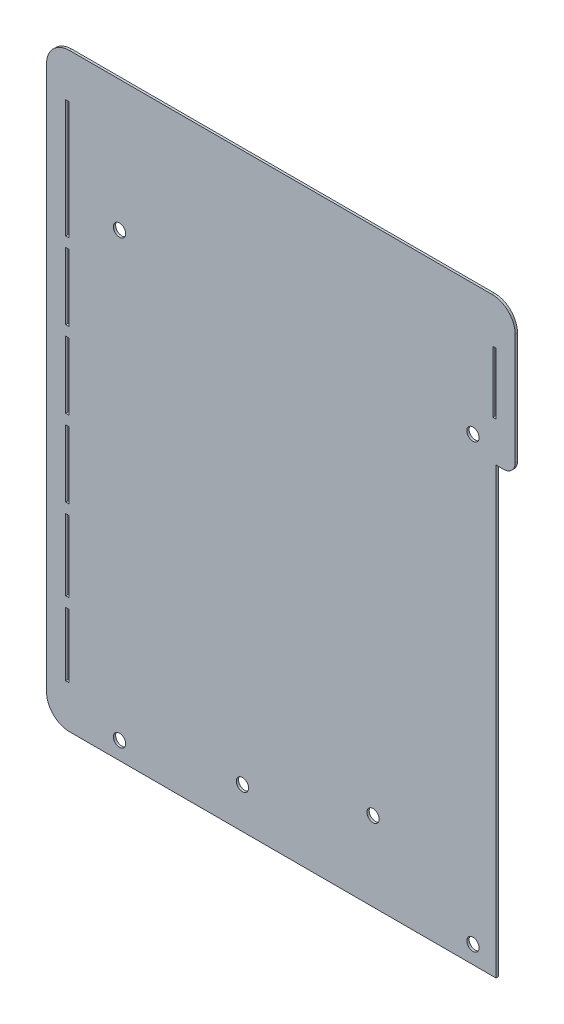
SolidWorks part; units mm, degrees
material "Plain Carbon Steel"
ref_plane "Front Plane" through (0, 0, 0) normal (0, 0, 1) x (1, 0, 0)
ref_plane "Top Plane" through (0, 0, 0) normal (0, 1, 0) x (1, 0, 0)
ref_plane "Right Plane" through (0, 0, 0) normal (1, 0, 0) x (0, 0, -1)
sketch "Model" plane through (0, 0, 0) normal (0, 0, 1) x (1, 0, 0)
  line L0 (104.1673, 32.1811) -> (4.1672, 32.1811)
  line L1 (104.1673, 155.1806) -> (104.1673, 32.1811)
  line L2 (4.1672, 155.1806) -> (104.1673, 155.1806)
  line L3 (4.1672, 32.1811) -> (4.1672, 155.1806)
  line L4 (44.9158, 146.4259) -> (47.4224, 146.4259)
  line L5 (47.4224, 146.4259) -> (47.4224, 148.9326)
  line L6 (47.4224, 148.9326) -> (44.9158, 148.9326)
  line L7 (44.9158, 148.9326) -> (44.9158, 146.4259)
  line L8 (77.4127, 147.4278) -> (79.9193, 147.4278)
  line L9 (79.9193, 147.4278) -> (79.9193, 149.9344)
  line L10 (79.9193, 149.9344) -> (77.4127, 149.9344)
  line L11 (77.4127, 149.9344) -> (77.4127, 147.4278)
  line L12 (6.3266, 141.9721) -> (8.3592, 141.9721)
  line L13 (8.3592, 141.9721) -> (8.3592, 144.0047)
  line L14 (8.3592, 144.0047) -> (6.3266, 144.0047)
  line L15 (6.3266, 144.0047) -> (6.3266, 141.9721)
  line L16 (6.3266, 121.6529) -> (8.3592, 121.6529)
  line L17 (8.3592, 121.6529) -> (8.3592, 123.6855)
  line L18 (8.3592, 123.6855) -> (6.3266, 123.6855)
  line L19 (6.3266, 123.6855) -> (6.3266, 121.6529)
  line L20 (6.3266, 101.3324) -> (8.3592, 101.3324)
  line L21 (8.3592, 101.3324) -> (8.3592, 103.365)
  line L22 (8.3592, 103.365) -> (6.3266, 103.365)
  line L23 (6.3266, 103.365) -> (6.3266, 101.3324)
  line L24 (6.3266, 81.0118) -> (8.3592, 81.0118)
  line L25 (8.3592, 81.0118) -> (8.3592, 83.0444)
  line L26 (8.3592, 83.0444) -> (6.3266, 83.0444)
  line L27 (6.3266, 83.0444) -> (6.3266, 81.0118)
  line L28 (6.3266, 60.6927) -> (8.3592, 60.6927)
  line L29 (8.3592, 60.6927) -> (8.3592, 62.7253)
  line L30 (8.3592, 62.7253) -> (6.3266, 62.7253)
  line L31 (6.3266, 62.7253) -> (6.3266, 60.6927)
  line L32 (85.9221, 148.4144) -> (87.9547, 148.4144)
  line L33 (87.9547, 148.4144) -> (87.9547, 150.447)
  line L34 (87.9547, 150.447) -> (85.9221, 150.447)
  line L35 (85.9221, 150.447) -> (85.9221, 148.4144)
  line L36 (6.3266, 50.5324) -> (8.3592, 50.5324)
  line L37 (8.3592, 50.5324) -> (8.3592, 52.565)
  line L38 (8.3592, 52.565) -> (6.3266, 52.565)
  line L39 (6.3266, 52.565) -> (6.3266, 50.5324)
  line L40 (6.3266, 42.9118) -> (8.3592, 42.9118)
  line L41 (8.3592, 42.9118) -> (8.3592, 44.9444)
  line L42 (8.3592, 44.9444) -> (6.3266, 44.9444)
  line L43 (6.3266, 44.9444) -> (6.3266, 42.9118)
  line L44 (52.8726, 50.0418) -> (54.3815, 50.0418)
  line L45 (54.3815, 50.0418) -> (54.3815, 51.5508)
  line L46 (54.3815, 51.5508) -> (52.8726, 51.5508)
  line L47 (52.8726, 51.5508) -> (52.8726, 50.0418)
  line L48 (58.4219, 130.1637) -> (60.4545, 130.1637)
  line L49 (60.4545, 130.1637) -> (60.4545, 132.1963)
  line L50 (60.4545, 132.1963) -> (58.4219, 132.1963)
  line L51 (58.4219, 132.1963) -> (58.4219, 130.1637)
  line L52 (97.8807, 141.1439) -> (99.9133, 141.1439)
  line L53 (99.9133, 141.1439) -> (99.9133, 143.1765)
  line L54 (99.9133, 143.1765) -> (97.8807, 143.1765)
  line L55 (97.8807, 143.1765) -> (97.8807, 141.1439)
  line L56 (48.438, 37.3046) -> (48.438, 37.0552)
  line L57 (49.9456, 37.0552) -> (49.9456, 37.3046)
  line L58 (52.8877, 37.3046) -> (52.8877, 37.0552)
  line L59 (54.3967, 37.0552) -> (54.3967, 37.3046)
  line L60 (54.3126, 34.0993) -> (54.3126, 33.8995)
  line L61 (56.7201, 33.8995) -> (56.7201, 34.0993)
  line L62 (46.1133, 34.0993) -> (46.1133, 33.8995)
  line L63 (48.5207, 33.8995) -> (48.5207, 34.0993)
  line L64 (82.9607, 49.0165) -> (84.9933, 49.0165)
  line L65 (84.9933, 49.0165) -> (84.9933, 51.0492)
  line L66 (84.9933, 51.0492) -> (82.9607, 51.0492)
  line L67 (82.9607, 51.0492) -> (82.9607, 49.0165)
  line L68 (29.8828, 70.9163) -> (31.9154, 70.9163)
  line L69 (31.9154, 70.9163) -> (31.9154, 72.9489)
  line L70 (31.9154, 72.9489) -> (29.8828, 72.9489)
  line L71 (29.8828, 72.9489) -> (29.8828, 70.9163)
  line L72 (29.8828, 68.1658) -> (31.9154, 68.1658)
  line L73 (31.9154, 68.1658) -> (31.9154, 70.1984)
  line L74 (31.9154, 70.1984) -> (29.8828, 70.1984)
  line L75 (29.8828, 70.1984) -> (29.8828, 68.1658)
  line L76 (29.8828, 108.6649) -> (31.9154, 108.6649)
  line L77 (31.9154, 108.6649) -> (31.9154, 110.6975)
  line L78 (31.9154, 110.6975) -> (29.8828, 110.6975)
  line L79 (29.8828, 110.6975) -> (29.8828, 108.6649)
  line L80 (29.8828, 111.4141) -> (31.9154, 111.4141)
  line L81 (31.9154, 111.4141) -> (31.9154, 113.4467)
  line L82 (31.9154, 113.4467) -> (29.8828, 113.4467)
  line L83 (29.8828, 113.4467) -> (29.8828, 111.4141)
  line L84 (29.8828, 91.1652) -> (31.9154, 91.1652)
  line L85 (31.9154, 91.1652) -> (31.9154, 93.1978)
  line L86 (31.9154, 93.1978) -> (29.8828, 93.1978)
  line L87 (29.8828, 93.1978) -> (29.8828, 91.1652)
  line L88 (29.8828, 88.4147) -> (31.9154, 88.4147)
  line L89 (31.9154, 88.4147) -> (31.9154, 90.4473)
  line L90 (31.9154, 90.4473) -> (29.8828, 90.4473)
  line L91 (29.8828, 90.4473) -> (29.8828, 88.4147)
  line L92 (29.8828, 128.6658) -> (31.9154, 128.6658)
  line L93 (31.9154, 128.6658) -> (31.9154, 130.6984)
  line L94 (31.9154, 130.6984) -> (29.8828, 130.6984)
  line L95 (29.8828, 130.6984) -> (29.8828, 128.6658)
  line L96 (29.8828, 131.4163) -> (31.9154, 131.4163)
  line L97 (31.9154, 131.4163) -> (31.9154, 133.4489)
  line L98 (31.9154, 133.4489) -> (29.8828, 133.4489)
  line L99 (29.8828, 133.4489) -> (29.8828, 131.4163)
  line L100 (48.1611, 135.1453) -> (50.1937, 135.1453)
  line L101 (50.1937, 135.1453) -> (50.1937, 137.1779)
  line L102 (50.1937, 137.1779) -> (48.1611, 137.1779)
  line L103 (48.1611, 137.1779) -> (48.1611, 135.1453)
  line L104 (11.4074, 121.6529) -> (13.44, 121.6529)
  line L105 (13.44, 121.6529) -> (13.44, 123.6855)
  line L106 (13.44, 123.6855) -> (11.4074, 123.6855)
  line L107 (11.4074, 123.6855) -> (11.4074, 121.6529)
  line L108 (104.1673, 32.1811) -> (4.1672, 32.1811)
  line L109 (104.1673, 155.1806) -> (104.1673, 32.1811)
  line L110 (4.1672, 155.1806) -> (104.1673, 155.1806)
  line L111 (4.1672, 32.1811) -> (4.1672, 155.1806)
  spline S0 degree 3 poles (55.1711, 147.6799) (55.1711, 149.685) (52.1643, 149.685) (52.1643, 147.6799) knots 0 0 0 0 1 1 1 1
  spline S1 degree 3 poles (52.1643, 147.6799) (52.1643, 145.6749) (55.1711, 145.6749) (55.1711, 147.6799) knots 0 0 0 0 1 1 1 1
  spline S2 degree 3 poles (75.1706, 148.6804) (75.1706, 150.6854) (72.1637, 150.6854) (72.1637, 148.6804) knots 0 0 0 0 1 1 1 1
  spline S3 degree 3 poles (72.1637, 148.6804) (72.1637, 146.6754) (75.1706, 146.6754) (75.1706, 148.6804) knots 0 0 0 0 1 1 1 1
  spline S4 degree 3 poles (8.3592, 140.448) (8.3592, 141.8026) (6.3266, 141.8026) (6.3266, 140.448) knots 0 0 0 0 1 1 1 1
  spline S5 degree 3 poles (6.3266, 140.448) (6.3266, 139.0934) (8.3592, 139.0934) (8.3592, 140.448) knots 0 0 0 0 1 1 1 1
  spline S6 degree 3 poles (8.3592, 137.9083) (8.3592, 139.2629) (6.3266, 139.2629) (6.3266, 137.9083) knots 0 0 0 0 1 1 1 1
  spline S7 degree 3 poles (6.3266, 137.9083) (6.3266, 136.5537) (8.3592, 136.5537) (8.3592, 137.9083) knots 0 0 0 0 1 1 1 1
  spline S8 degree 3 poles (8.3592, 135.3686) (8.3592, 136.7232) (6.3266, 136.7232) (6.3266, 135.3686) knots 0 0 0 0 1 1 1 1
  spline S9 degree 3 poles (6.3266, 135.3686) (6.3266, 134.0139) (8.3592, 134.0139) (8.3592, 135.3686) knots 0 0 0 0 1 1 1 1
  spline S10 degree 3 poles (8.3592, 132.8288) (8.3592, 134.1834) (6.3266, 134.1834) (6.3266, 132.8288) knots 0 0 0 0 1 1 1 1
  spline S11 degree 3 poles (6.3266, 132.8288) (6.3266, 131.4742) (8.3592, 131.4742) (8.3592, 132.8288) knots 0 0 0 0 1 1 1 1
  spline S12 degree 3 poles (8.3592, 130.2891) (8.3592, 131.6437) (6.3266, 131.6437) (6.3266, 130.2891) knots 0 0 0 0 1 1 1 1
  spline S13 degree 3 poles (6.3266, 130.2891) (6.3266, 128.9331) (8.3592, 128.9331) (8.3592, 130.2891) knots 0 0 0 0 1 1 1 1
  spline S14 degree 3 poles (8.3592, 127.748) (8.3592, 129.1026) (6.3266, 129.1026) (6.3266, 127.748) knots 0 0 0 0 1 1 1 1
  spline S15 degree 3 poles (6.3266, 127.748) (6.3266, 126.3934) (8.3592, 126.3934) (8.3592, 127.748) knots 0 0 0 0 1 1 1 1
  spline S16 degree 3 poles (8.3592, 120.1288) (8.3592, 121.4834) (6.3266, 121.4834) (6.3266, 120.1288) knots 0 0 0 0 1 1 1 1
  spline S17 degree 3 poles (6.3266, 120.1288) (6.3266, 118.7742) (8.3592, 118.7742) (8.3592, 120.1288) knots 0 0 0 0 1 1 1 1
  spline S18 degree 3 poles (8.3592, 117.5891) (8.3592, 118.9437) (6.3266, 118.9437) (6.3266, 117.5891) knots 0 0 0 0 1 1 1 1
  spline S19 degree 3 poles (6.3266, 117.5891) (6.3266, 116.2331) (8.3592, 116.2331) (8.3592, 117.5891) knots 0 0 0 0 1 1 1 1
  spline S20 degree 3 poles (8.3592, 115.048) (8.3592, 116.4026) (6.3266, 116.4026) (6.3266, 115.048) knots 0 0 0 0 1 1 1 1
  spline S21 degree 3 poles (6.3266, 115.048) (6.3266, 113.6934) (8.3592, 113.6934) (8.3592, 115.048) knots 0 0 0 0 1 1 1 1
  spline S22 degree 3 poles (8.3592, 112.5083) (8.3592, 113.8629) (6.3266, 113.8629) (6.3266, 112.5083) knots 0 0 0 0 1 1 1 1
  spline S23 degree 3 poles (6.3266, 112.5083) (6.3266, 111.1537) (8.3592, 111.1537) (8.3592, 112.5083) knots 0 0 0 0 1 1 1 1
  spline S24 degree 3 poles (8.3592, 109.9686) (8.3592, 111.3232) (6.3266, 111.3232) (6.3266, 109.9686) knots 0 0 0 0 1 1 1 1
  spline S25 degree 3 poles (6.3266, 109.9686) (6.3266, 108.6139) (8.3592, 108.6139) (8.3592, 109.9686) knots 0 0 0 0 1 1 1 1
  spline S26 degree 3 poles (8.3592, 107.4288) (8.3592, 108.7834) (6.3266, 108.7834) (6.3266, 107.4288) knots 0 0 0 0 1 1 1 1
  spline S27 degree 3 poles (6.3266, 107.4288) (6.3266, 106.0742) (8.3592, 106.0742) (8.3592, 107.4288) knots 0 0 0 0 1 1 1 1
  spline S28 degree 3 poles (8.3592, 99.8083) (8.3592, 101.1629) (6.3266, 101.1629) (6.3266, 99.8083) knots 0 0 0 0 1 1 1 1
  spline S29 degree 3 poles (6.3266, 99.8083) (6.3266, 98.4537) (8.3592, 98.4537) (8.3592, 99.8083) knots 0 0 0 0 1 1 1 1
  spline S30 degree 3 poles (8.3592, 97.2686) (8.3592, 98.6232) (6.3266, 98.6232) (6.3266, 97.2686) knots 0 0 0 0 1 1 1 1
  spline S31 degree 3 poles (6.3266, 97.2686) (6.3266, 95.9139) (8.3592, 95.9139) (8.3592, 97.2686) knots 0 0 0 0 1 1 1 1
  spline S32 degree 3 poles (8.3592, 94.7288) (8.3592, 96.0834) (6.3266, 96.0834) (6.3266, 94.7288) knots 0 0 0 0 1 1 1 1
  spline S33 degree 3 poles (6.3266, 94.7288) (6.3266, 93.3742) (8.3592, 93.3742) (8.3592, 94.7288) knots 0 0 0 0 1 1 1 1
  spline S34 degree 3 poles (8.3592, 92.1891) (8.3592, 93.5437) (6.3266, 93.5437) (6.3266, 92.1891) knots 0 0 0 0 1 1 1 1
  spline S35 degree 3 poles (6.3266, 92.1891) (6.3266, 90.8331) (8.3592, 90.8331) (8.3592, 92.1891) knots 0 0 0 0 1 1 1 1
  spline S36 degree 3 poles (8.3592, 89.648) (8.3592, 91.0026) (6.3266, 91.0026) (6.3266, 89.648) knots 0 0 0 0 1 1 1 1
  spline S37 degree 3 poles (6.3266, 89.648) (6.3266, 88.2934) (8.3592, 88.2934) (8.3592, 89.648) knots 0 0 0 0 1 1 1 1
  spline S38 degree 3 poles (8.3592, 87.1083) (8.3592, 88.4629) (6.3266, 88.4629) (6.3266, 87.1083) knots 0 0 0 0 1 1 1 1
  spline S39 degree 3 poles (6.3266, 87.1083) (6.3266, 85.7537) (8.3592, 85.7537) (8.3592, 87.1083) knots 0 0 0 0 1 1 1 1
  spline S40 degree 3 poles (8.3592, 79.4891) (8.3592, 80.8437) (6.3266, 80.8437) (6.3266, 79.4891) knots 0 0 0 0 1 1 1 1
  spline S41 degree 3 poles (6.3266, 79.4891) (6.3266, 78.1331) (8.3592, 78.1331) (8.3592, 79.4891) knots 0 0 0 0 1 1 1 1
  spline S42 degree 3 poles (8.3592, 76.948) (8.3592, 78.3026) (6.3266, 78.3026) (6.3266, 76.948) knots 0 0 0 0 1 1 1 1
  spline S43 degree 3 poles (6.3266, 76.948) (6.3266, 75.5934) (8.3592, 75.5934) (8.3592, 76.948) knots 0 0 0 0 1 1 1 1
  spline S44 degree 3 poles (8.3592, 74.4083) (8.3592, 75.7629) (6.3266, 75.7629) (6.3266, 74.4083) knots 0 0 0 0 1 1 1 1
  spline S45 degree 3 poles (6.3266, 74.4083) (6.3266, 73.0537) (8.3592, 73.0537) (8.3592, 74.4083) knots 0 0 0 0 1 1 1 1
  spline S46 degree 3 poles (8.3592, 71.8685) (8.3592, 73.2232) (6.3266, 73.2232) (6.3266, 71.8685) knots 0 0 0 0 1 1 1 1
  spline S47 degree 3 poles (6.3266, 71.8685) (6.3266, 70.5139) (8.3592, 70.5139) (8.3592, 71.8685) knots 0 0 0 0 1 1 1 1
  spline S48 degree 3 poles (8.3592, 69.3288) (8.3592, 70.6834) (6.3266, 70.6834) (6.3266, 69.3288) knots 0 0 0 0 1 1 1 1
  spline S49 degree 3 poles (6.3266, 69.3288) (6.3266, 67.9742) (8.3592, 67.9742) (8.3592, 69.3288) knots 0 0 0 0 1 1 1 1
  spline S50 degree 3 poles (8.3592, 66.7891) (8.3592, 68.1437) (6.3266, 68.1437) (6.3266, 66.7891) knots 0 0 0 0 1 1 1 1
  spline S51 degree 3 poles (6.3266, 66.7891) (6.3266, 65.4331) (8.3592, 65.4331) (8.3592, 66.7891) knots 0 0 0 0 1 1 1 1
  spline S52 degree 3 poles (8.3592, 59.1686) (8.3592, 60.5232) (6.3266, 60.5232) (6.3266, 59.1686) knots 0 0 0 0 1 1 1 1
  spline S53 degree 3 poles (6.3266, 59.1686) (6.3266, 57.8139) (8.3592, 57.8139) (8.3592, 59.1686) knots 0 0 0 0 1 1 1 1
  spline S54 degree 3 poles (8.3592, 56.6288) (8.3592, 57.9834) (6.3266, 57.9834) (6.3266, 56.6288) knots 0 0 0 0 1 1 1 1
  spline S55 degree 3 poles (6.3266, 56.6288) (6.3266, 55.2742) (8.3592, 55.2742) (8.3592, 56.6288) knots 0 0 0 0 1 1 1 1
  spline S56 degree 3 poles (8.3592, 54.0891) (8.3592, 55.4437) (6.3266, 55.4437) (6.3266, 54.0891) knots 0 0 0 0 1 1 1 1
  spline S57 degree 3 poles (6.3266, 54.0891) (6.3266, 52.7331) (8.3592, 52.7331) (8.3592, 54.0891) knots 0 0 0 0 1 1 1 1
  spline S58 degree 3 poles (85.4149, 149.4301) (85.4149, 150.7847) (83.3823, 150.7847) (83.3823, 149.4301) knots 0 0 0 0 1 1 1 1
  spline S59 degree 3 poles (83.3823, 149.4301) (83.3823, 148.0754) (85.4149, 148.0754) (85.4149, 149.4301) knots 0 0 0 0 1 1 1 1
  spline S60 degree 3 poles (8.3592, 49.0083) (8.3592, 50.3629) (6.3266, 50.3629) (6.3266, 49.0083) knots 0 0 0 0 1 1 1 1
  spline S61 degree 3 poles (6.3266, 49.0083) (6.3266, 47.6537) (8.3592, 47.6537) (8.3592, 49.0083) knots 0 0 0 0 1 1 1 1
  spline S62 degree 3 poles (8.3592, 41.3891) (8.3592, 42.7437) (6.3266, 42.7437) (6.3266, 41.3891) knots 0 0 0 0 1 1 1 1
  spline S63 degree 3 poles (6.3266, 41.3891) (6.3266, 40.0331) (8.3592, 40.0331) (8.3592, 41.3891) knots 0 0 0 0 1 1 1 1
  spline S64 degree 3 poles (54.3815, 52.0661) (54.3815, 53.0721) (52.8726, 53.0721) (52.8726, 52.0661) knots 0 0 0 0 1 1 1 1
  spline S65 degree 3 poles (52.8726, 52.0661) (52.8726, 51.0602) (54.3815, 51.0602) (54.3815, 52.0661) knots 0 0 0 0 1 1 1 1
  spline S66 degree 3 poles (55.6507, 50.797) (55.6507, 51.8029) (54.1417, 51.8029) (54.1417, 50.797) knots 0 0 0 0 1 1 1 1
  spline S67 degree 3 poles (54.1417, 50.797) (54.1417, 49.791) (55.6507, 49.791) (55.6507, 50.797) knots 0 0 0 0 1 1 1 1
  spline S68 degree 3 poles (55.6507, 52.0661) (55.6507, 53.0721) (54.1417, 53.0721) (54.1417, 52.0661) knots 0 0 0 0 1 1 1 1
  spline S69 degree 3 poles (54.1417, 52.0661) (54.1417, 51.0602) (55.6507, 51.0602) (55.6507, 52.0661) knots 0 0 0 0 1 1 1 1
  spline S70 degree 3 poles (56.9212, 50.797) (56.9212, 51.8029) (55.4123, 51.8029) (55.4123, 50.797) knots 0 0 0 0 1 1 1 1
  spline S71 degree 3 poles (55.4123, 50.797) (55.4123, 49.791) (56.9212, 49.791) (56.9212, 50.797) knots 0 0 0 0 1 1 1 1
  spline S72 degree 3 poles (56.9212, 52.0661) (56.9212, 53.0721) (55.4123, 53.0721) (55.4123, 52.0661) knots 0 0 0 0 1 1 1 1
  spline S73 degree 3 poles (55.4123, 52.0661) (55.4123, 51.0602) (56.9212, 51.0602) (56.9212, 52.0661) knots 0 0 0 0 1 1 1 1
  spline S74 degree 3 poles (58.1904, 50.797) (58.1904, 51.8029) (56.6828, 51.8029) (56.6828, 50.797) knots 0 0 0 0 1 1 1 1
  spline S75 degree 3 poles (56.6828, 50.797) (56.6828, 49.791) (58.1904, 49.791) (58.1904, 50.797) knots 0 0 0 0 1 1 1 1
  spline S76 degree 3 poles (58.1904, 52.0661) (58.1904, 53.0721) (56.6828, 53.0721) (56.6828, 52.0661) knots 0 0 0 0 1 1 1 1
  spline S77 degree 3 poles (56.6828, 52.0661) (56.6828, 51.0602) (58.1904, 51.0602) (58.1904, 52.0661) knots 0 0 0 0 1 1 1 1
  spline S78 degree 3 poles (59.461, 50.797) (59.461, 51.8029) (57.952, 51.8029) (57.952, 50.797) knots 0 0 0 0 1 1 1 1
  spline S79 degree 3 poles (57.952, 50.797) (57.952, 49.791) (59.461, 49.791) (59.461, 50.797) knots 0 0 0 0 1 1 1 1
  spline S80 degree 3 poles (59.461, 52.0661) (59.461, 53.0721) (57.952, 53.0721) (57.952, 52.0661) knots 0 0 0 0 1 1 1 1
  spline S81 degree 3 poles (57.952, 52.0661) (57.952, 51.0602) (59.461, 51.0602) (59.461, 52.0661) knots 0 0 0 0 1 1 1 1
  spline S82 degree 3 poles (57.9148, 131.1793) (57.9148, 132.5353) (55.8822, 132.5353) (55.8822, 131.1793) knots 0 0 0 0 1 1 1 1
  spline S83 degree 3 poles (55.8822, 131.1793) (55.8822, 129.8247) (57.9148, 129.8247) (57.9148, 131.1793) knots 0 0 0 0 1 1 1 1
  spline S84 degree 3 poles (63.2437, 36.9311) (63.2437, 37.9371) (61.7347, 37.9371) (61.7347, 36.9311) knots 0 0 0 0 1 1 1 1
  spline S85 degree 3 poles (61.7347, 36.9311) (61.7347, 35.9252) (63.2437, 35.9252) (63.2437, 36.9311) knots 0 0 0 0 1 1 1 1
  spline S86 degree 3 poles (71.2239, 36.9311) (71.2239, 37.9371) (69.715, 37.9371) (69.715, 36.9311) knots 0 0 0 0 1 1 1 1
  spline S87 degree 3 poles (69.715, 36.9311) (69.715, 35.9252) (71.2239, 35.9252) (71.2239, 36.9311) knots 0 0 0 0 1 1 1 1
  spline S88 degree 3 poles (102.453, 142.1609) (102.453, 143.5155) (100.4204, 143.5155) (100.4204, 142.1609) knots 0 0 0 0 1 1 1 1
  spline S89 degree 3 poles (100.4204, 142.1609) (100.4204, 140.8063) (102.453, 140.8063) (102.453, 142.1609) knots 0 0 0 0 1 1 1 1
  spline S90 degree 3 poles (99.9133, 129.4609) (99.9133, 130.8155) (97.8807, 130.8155) (97.8807, 129.4609) knots 0 0 0 0 1 1 1 1
  spline S91 degree 3 poles (97.8807, 129.4609) (97.8807, 128.1063) (99.9133, 128.1063) (99.9133, 129.4609) knots 0 0 0 0 1 1 1 1
  spline S92 degree 3 poles (102.453, 139.6198) (102.453, 140.9744) (100.4204, 140.9744) (100.4204, 139.6198) knots 0 0 0 0 1 1 1 1
  spline S93 degree 3 poles (100.4204, 139.6198) (100.4204, 138.2652) (102.453, 138.2652) (102.453, 139.6198) knots 0 0 0 0 1 1 1 1
  spline S94 degree 3 poles (99.9133, 126.9198) (99.9133, 128.2744) (97.8807, 128.2744) (97.8807, 126.9198) knots 0 0 0 0 1 1 1 1
  spline S95 degree 3 poles (97.8807, 126.9198) (97.8807, 125.5652) (99.9133, 125.5652) (99.9133, 126.9198) knots 0 0 0 0 1 1 1 1
  spline S96 degree 3 poles (102.453, 137.0801) (102.453, 138.4347) (100.4204, 138.4347) (100.4204, 137.0801) knots 0 0 0 0 1 1 1 1
  spline S97 degree 3 poles (100.4204, 137.0801) (100.4204, 135.7255) (102.453, 135.7255) (102.453, 137.0801) knots 0 0 0 0 1 1 1 1
  spline S98 degree 3 poles (99.9133, 124.3801) (99.9133, 125.7347) (97.8807, 125.7347) (97.8807, 124.3801) knots 0 0 0 0 1 1 1 1
  spline S99 degree 3 poles (97.8807, 124.3801) (97.8807, 123.0255) (99.9133, 123.0255) (99.9133, 124.3801) knots 0 0 0 0 1 1 1 1
  spline S100 degree 3 poles (102.453, 134.5403) (102.453, 135.895) (100.4204, 135.895) (100.4204, 134.5403) knots 0 0 0 0 1 1 1 1
  spline S101 degree 3 poles (100.4204, 134.5403) (100.4204, 133.1857) (102.453, 133.1857) (102.453, 134.5403) knots 0 0 0 0 1 1 1 1
  spline S102 degree 3 poles (99.9133, 121.8404) (99.9133, 123.195) (97.8807, 123.195) (97.8807, 121.8404) knots 0 0 0 0 1 1 1 1
  spline S103 degree 3 poles (97.8807, 121.8404) (97.8807, 120.4857) (99.9133, 120.4857) (99.9133, 121.8404) knots 0 0 0 0 1 1 1 1
  spline S104 degree 3 poles (102.453, 132.0006) (102.453, 133.3552) (100.4204, 133.3552) (100.4204, 132.0006) knots 0 0 0 0 1 1 1 1
  spline S105 degree 3 poles (100.4204, 132.0006) (100.4204, 130.646) (102.453, 130.646) (102.453, 132.0006) knots 0 0 0 0 1 1 1 1
  spline S106 degree 3 poles (99.9133, 119.3006) (99.9133, 120.6552) (97.8807, 120.6552) (97.8807, 119.3006) knots 0 0 0 0 1 1 1 1
  spline S107 degree 3 poles (97.8807, 119.3006) (97.8807, 117.946) (99.9133, 117.946) (99.9133, 119.3006) knots 0 0 0 0 1 1 1 1
  spline S108 degree 3 poles (102.453, 129.4609) (102.453, 130.8155) (100.4204, 130.8155) (100.4204, 129.4609) knots 0 0 0 0 1 1 1 1
  spline S109 degree 3 poles (100.4204, 129.4609) (100.4204, 128.1063) (102.453, 128.1063) (102.453, 129.4609) knots 0 0 0 0 1 1 1 1
  spline S110 degree 3 poles (99.9133, 116.7609) (99.9133, 118.1155) (97.8807, 118.1155) (97.8807, 116.7609) knots 0 0 0 0 1 1 1 1
  spline S111 degree 3 poles (97.8807, 116.7609) (97.8807, 115.4063) (99.9133, 115.4063) (99.9133, 116.7609) knots 0 0 0 0 1 1 1 1
  spline S112 degree 3 poles (102.453, 126.9198) (102.453, 128.2744) (100.4204, 128.2744) (100.4204, 126.9198) knots 0 0 0 0 1 1 1 1
  spline S113 degree 3 poles (100.4204, 126.9198) (100.4204, 125.5652) (102.453, 125.5652) (102.453, 126.9198) knots 0 0 0 0 1 1 1 1
  spline S114 degree 3 poles (99.9133, 114.2198) (99.9133, 115.5744) (97.8807, 115.5744) (97.8807, 114.2198) knots 0 0 0 0 1 1 1 1
  spline S115 degree 3 poles (97.8807, 114.2198) (97.8807, 112.8652) (99.9133, 112.8652) (99.9133, 114.2198) knots 0 0 0 0 1 1 1 1
  spline S116 degree 3 poles (102.453, 124.3801) (102.453, 125.7347) (100.4204, 125.7347) (100.4204, 124.3801) knots 0 0 0 0 1 1 1 1
  spline S117 degree 3 poles (100.4204, 124.3801) (100.4204, 123.0255) (102.453, 123.0255) (102.453, 124.3801) knots 0 0 0 0 1 1 1 1
  spline S118 degree 3 poles (99.9133, 111.6801) (99.9133, 113.0347) (97.8807, 113.0347) (97.8807, 111.6801) knots 0 0 0 0 1 1 1 1
  spline S119 degree 3 poles (97.8807, 111.6801) (97.8807, 110.3255) (99.9133, 110.3255) (99.9133, 111.6801) knots 0 0 0 0 1 1 1 1
  spline S120 degree 3 poles (102.453, 121.8404) (102.453, 123.195) (100.4204, 123.195) (100.4204, 121.8404) knots 0 0 0 0 1 1 1 1
  spline S121 degree 3 poles (100.4204, 121.8404) (100.4204, 120.4857) (102.453, 120.4857) (102.453, 121.8404) knots 0 0 0 0 1 1 1 1
  spline S122 degree 3 poles (99.9133, 109.1404) (99.9133, 110.495) (97.8807, 110.495) (97.8807, 109.1404) knots 0 0 0 0 1 1 1 1
  spline S123 degree 3 poles (97.8807, 109.1404) (97.8807, 107.7857) (99.9133, 107.7857) (99.9133, 109.1404) knots 0 0 0 0 1 1 1 1
  spline S124 degree 3 poles (102.453, 119.3006) (102.453, 120.6552) (100.4204, 120.6552) (100.4204, 119.3006) knots 0 0 0 0 1 1 1 1
  spline S125 degree 3 poles (100.4204, 119.3006) (100.4204, 117.946) (102.453, 117.946) (102.453, 119.3006) knots 0 0 0 0 1 1 1 1
  spline S126 degree 3 poles (99.9133, 106.6006) (99.9133, 107.9552) (97.8807, 107.9552) (97.8807, 106.6006) knots 0 0 0 0 1 1 1 1
  spline S127 degree 3 poles (97.8807, 106.6006) (97.8807, 105.246) (99.9133, 105.246) (99.9133, 106.6006) knots 0 0 0 0 1 1 1 1
  spline S128 degree 3 poles (102.453, 116.7609) (102.453, 118.1155) (100.4204, 118.1155) (100.4204, 116.7609) knots 0 0 0 0 1 1 1 1
  spline S129 degree 3 poles (100.4204, 116.7609) (100.4204, 115.4063) (102.453, 115.4063) (102.453, 116.7609) knots 0 0 0 0 1 1 1 1
  spline S130 degree 3 poles (99.9133, 104.0609) (99.9133, 105.4155) (97.8807, 105.4155) (97.8807, 104.0609) knots 0 0 0 0 1 1 1 1
  spline S131 degree 3 poles (97.8807, 104.0609) (97.8807, 102.7063) (99.9133, 102.7063) (99.9133, 104.0609) knots 0 0 0 0 1 1 1 1
  spline S132 degree 3 poles (102.453, 114.2198) (102.453, 115.5744) (100.4204, 115.5744) (100.4204, 114.2198) knots 0 0 0 0 1 1 1 1
  spline S133 degree 3 poles (100.4204, 114.2198) (100.4204, 112.8652) (102.453, 112.8652) (102.453, 114.2198) knots 0 0 0 0 1 1 1 1
  spline S134 degree 3 poles (102.453, 111.6801) (102.453, 113.0347) (100.4204, 113.0347) (100.4204, 111.6801) knots 0 0 0 0 1 1 1 1
  spline S135 degree 3 poles (100.4204, 111.6801) (100.4204, 110.3255) (102.453, 110.3255) (102.453, 111.6801) knots 0 0 0 0 1 1 1 1
  spline S136 degree 3 poles (99.9133, 101.5198) (99.9133, 102.8744) (97.8807, 102.8744) (97.8807, 101.5198) knots 0 0 0 0 1 1 1 1
  spline S137 degree 3 poles (97.8807, 101.5198) (97.8807, 100.1652) (99.9133, 100.1652) (99.9133, 101.5198) knots 0 0 0 0 1 1 1 1
  spline S138 degree 3 poles (102.453, 109.1404) (102.453, 110.495) (100.4204, 110.495) (100.4204, 109.1404) knots 0 0 0 0 1 1 1 1
  spline S139 degree 3 poles (100.4204, 109.1404) (100.4204, 107.7857) (102.453, 107.7857) (102.453, 109.1404) knots 0 0 0 0 1 1 1 1
  spline S140 degree 3 poles (102.453, 104.0609) (102.453, 105.4155) (100.4204, 105.4155) (100.4204, 104.0609) knots 0 0 0 0 1 1 1 1
  spline S141 degree 3 poles (100.4204, 104.0609) (100.4204, 102.7063) (102.453, 102.7063) (102.453, 104.0609) knots 0 0 0 0 1 1 1 1
  spline S142 degree 3 poles (102.453, 101.5198) (102.453, 102.8744) (100.4204, 102.8744) (100.4204, 101.5198) knots 0 0 0 0 1 1 1 1
  spline S143 degree 3 poles (100.4204, 101.5198) (100.4204, 100.1652) (102.453, 100.1652) (102.453, 101.5198) knots 0 0 0 0 1 1 1 1
  spline S144 degree 3 poles (102.453, 98.9801) (102.453, 100.3347) (100.4204, 100.3347) (100.4204, 98.9801) knots 0 0 0 0 1 1 1 1
  spline S145 degree 3 poles (100.4204, 98.9801) (100.4204, 97.6255) (102.453, 97.6255) (102.453, 98.9801) knots 0 0 0 0 1 1 1 1
  spline S146 degree 3 poles (102.453, 96.4404) (102.453, 97.795) (100.4204, 97.795) (100.4204, 96.4404) knots 0 0 0 0 1 1 1 1
  spline S147 degree 3 poles (100.4204, 96.4404) (100.4204, 95.0857) (102.453, 95.0857) (102.453, 96.4404) knots 0 0 0 0 1 1 1 1
  spline S148 degree 3 poles (99.9133, 98.9801) (99.9133, 100.3347) (97.8807, 100.3347) (97.8807, 98.9801) knots 0 0 0 0 1 1 1 1
  spline S149 degree 3 poles (97.8807, 98.9801) (97.8807, 97.6255) (99.9133, 97.6255) (99.9133, 98.9801) knots 0 0 0 0 1 1 1 1
  spline S150 degree 3 poles (99.9133, 96.4404) (99.9133, 97.795) (97.8807, 97.795) (97.8807, 96.4404) knots 0 0 0 0 1 1 1 1
  spline S151 degree 3 poles (97.8807, 96.4404) (97.8807, 95.0857) (99.9133, 95.0857) (99.9133, 96.4404) knots 0 0 0 0 1 1 1 1
  spline S152 degree 3 poles (99.9133, 139.6198) (99.9133, 140.9744) (97.8807, 140.9744) (97.8807, 139.6198) knots 0 0 0 0 1 1 1 1
  spline S153 degree 3 poles (97.8807, 139.6198) (97.8807, 138.2652) (99.9133, 138.2652) (99.9133, 139.6198) knots 0 0 0 0 1 1 1 1
  spline S154 degree 3 poles (99.9133, 137.0801) (99.9133, 138.4347) (97.8807, 138.4347) (97.8807, 137.0801) knots 0 0 0 0 1 1 1 1
  spline S155 degree 3 poles (97.8807, 137.0801) (97.8807, 135.7255) (99.9133, 135.7255) (99.9133, 137.0801) knots 0 0 0 0 1 1 1 1
  spline S156 degree 3 poles (99.9133, 134.5403) (99.9133, 135.895) (97.8807, 135.895) (97.8807, 134.5403) knots 0 0 0 0 1 1 1 1
  spline S157 degree 3 poles (97.8807, 134.5403) (97.8807, 133.1857) (99.9133, 133.1857) (99.9133, 134.5403) knots 0 0 0 0 1 1 1 1
  spline S158 degree 3 poles (99.9133, 132.0006) (99.9133, 133.3552) (97.8807, 133.3552) (97.8807, 132.0006) knots 0 0 0 0 1 1 1 1
  spline S159 degree 3 poles (97.8807, 132.0006) (97.8807, 130.646) (99.9133, 130.646) (99.9133, 132.0006) knots 0 0 0 0 1 1 1 1
  spline S160 degree 3 poles (99.9133, 93.9006) (99.9133, 95.2552) (97.8807, 95.2552) (97.8807, 93.9006) knots 0 0 0 0 1 1 1 1
  spline S161 degree 3 poles (97.8807, 93.9006) (97.8807, 92.546) (99.9133, 92.546) (99.9133, 93.9006) knots 0 0 0 0 1 1 1 1
  spline S162 degree 3 poles (102.453, 93.9006) (102.453, 95.2552) (100.4204, 95.2552) (100.4204, 93.9006) knots 0 0 0 0 1 1 1 1
  spline S163 degree 3 poles (100.4204, 93.9006) (100.4204, 92.546) (102.453, 92.546) (102.453, 93.9006) knots 0 0 0 0 1 1 1 1
  spline S164 degree 3 poles (102.453, 106.6006) (102.453, 107.9552) (100.4204, 107.9552) (100.4204, 106.6006) knots 0 0 0 0 1 1 1 1
  spline S165 degree 3 poles (100.4204, 106.6006) (100.4204, 105.246) (102.453, 105.246) (102.453, 106.6006) knots 0 0 0 0 1 1 1 1
  spline S166 degree 3 poles (99.9133, 91.3609) (99.9133, 92.7155) (97.8807, 92.7155) (97.8807, 91.3609) knots 0 0 0 0 1 1 1 1
  spline S167 degree 3 poles (97.8807, 91.3609) (97.8807, 90.0063) (99.9133, 90.0063) (99.9133, 91.3609) knots 0 0 0 0 1 1 1 1
  spline S168 degree 3 poles (102.453, 91.3609) (102.453, 92.7155) (100.4204, 92.7155) (100.4204, 91.3609) knots 0 0 0 0 1 1 1 1
  spline S169 degree 3 poles (100.4204, 91.3609) (100.4204, 90.0063) (102.453, 90.0063) (102.453, 91.3609) knots 0 0 0 0 1 1 1 1
  spline S170 degree 3 poles (99.9133, 88.8198) (99.9133, 90.1744) (97.8807, 90.1744) (97.8807, 88.8198) knots 0 0 0 0 1 1 1 1
  spline S171 degree 3 poles (97.8807, 88.8198) (97.8807, 87.4652) (99.9133, 87.4652) (99.9133, 88.8198) knots 0 0 0 0 1 1 1 1
  spline S172 degree 3 poles (102.453, 88.8198) (102.453, 90.1744) (100.4204, 90.1744) (100.4204, 88.8198) knots 0 0 0 0 1 1 1 1
  spline S173 degree 3 poles (100.4204, 88.8198) (100.4204, 87.4652) (102.453, 87.4652) (102.453, 88.8198) knots 0 0 0 0 1 1 1 1
  spline S174 degree 3 poles (99.9133, 86.2801) (99.9133, 87.6347) (97.8807, 87.6347) (97.8807, 86.2801) knots 0 0 0 0 1 1 1 1
  spline S175 degree 3 poles (97.8807, 86.2801) (97.8807, 84.9255) (99.9133, 84.9255) (99.9133, 86.2801) knots 0 0 0 0 1 1 1 1
  spline S176 degree 3 poles (102.453, 86.2801) (102.453, 87.6347) (100.4204, 87.6347) (100.4204, 86.2801) knots 0 0 0 0 1 1 1 1
  spline S177 degree 3 poles (100.4204, 86.2801) (100.4204, 84.9255) (102.453, 84.9255) (102.453, 86.2801) knots 0 0 0 0 1 1 1 1
  spline S178 degree 3 poles (99.9133, 83.7404) (99.9133, 85.095) (97.8807, 85.095) (97.8807, 83.7404) knots 0 0 0 0 1 1 1 1
  spline S179 degree 3 poles (97.8807, 83.7404) (97.8807, 82.3857) (99.9133, 82.3857) (99.9133, 83.7404) knots 0 0 0 0 1 1 1 1
  spline S180 degree 3 poles (102.453, 83.7404) (102.453, 85.095) (100.4204, 85.095) (100.4204, 83.7404) knots 0 0 0 0 1 1 1 1
  spline S181 degree 3 poles (100.4204, 83.7404) (100.4204, 82.3857) (102.453, 82.3857) (102.453, 83.7404) knots 0 0 0 0 1 1 1 1
  spline S182 degree 3 poles (99.9133, 81.2006) (99.9133, 82.5552) (97.8807, 82.5552) (97.8807, 81.2006) knots 0 0 0 0 1 1 1 1
  spline S183 degree 3 poles (97.8807, 81.2006) (97.8807, 79.846) (99.9133, 79.846) (99.9133, 81.2006) knots 0 0 0 0 1 1 1 1
  spline S184 degree 3 poles (102.453, 81.2006) (102.453, 82.5552) (100.4204, 82.5552) (100.4204, 81.2006) knots 0 0 0 0 1 1 1 1
  spline S185 degree 3 poles (100.4204, 81.2006) (100.4204, 79.846) (102.453, 79.846) (102.453, 81.2006) knots 0 0 0 0 1 1 1 1
  spline S186 degree 3 poles (49.9456, 37.3046) (49.9456, 38.3106) (48.438, 38.3106) (48.438, 37.3046) knots 0 0 0 0 1 1 1 1
  spline S187 degree 3 poles (48.438, 37.0552) (48.438, 36.0492) (49.9456, 36.0492) (49.9456, 37.0552) knots 0 0 0 0 1 1 1 1
  spline S188 degree 3 poles (54.3967, 37.3046) (54.3967, 38.3106) (52.8877, 38.3106) (52.8877, 37.3046) knots 0 0 0 0 1 1 1 1
  spline S189 degree 3 poles (52.8877, 37.0552) (52.8877, 36.0492) (54.3967, 36.0492) (54.3967, 37.0552) knots 0 0 0 0 1 1 1 1
  spline S190 degree 3 poles (56.7201, 34.0993) (56.7201, 35.7047) (54.3126, 35.7047) (54.3126, 34.0993) knots 0 0 0 0 1 1 1 1
  spline S191 degree 3 poles (54.3126, 33.8995) (54.3126, 32.2941) (56.7201, 32.2941) (56.7201, 33.8995) knots 0 0 0 0 1 1 1 1
  spline S192 degree 3 poles (48.5207, 34.0993) (48.5207, 35.7047) (46.1133, 35.7047) (46.1133, 34.0993) knots 0 0 0 0 1 1 1 1
  spline S193 degree 3 poles (46.1133, 33.8995) (46.1133, 32.2941) (48.5207, 32.2941) (48.5207, 33.8995) knots 0 0 0 0 1 1 1 1
  spline S194 degree 3 poles (54.4711, 34.0001) (54.4711, 34.9054) (53.1123, 34.9054) (53.1123, 34.0001) knots 0 0 0 0 1 1 1 1
  spline S195 degree 3 poles (53.1123, 34.0001) (53.1123, 33.0933) (54.4711, 33.0933) (54.4711, 34.0001) knots 0 0 0 0 1 1 1 1
  spline S196 degree 3 poles (49.721, 34.0001) (49.721, 34.9054) (48.3623, 34.9054) (48.3623, 34.0001) knots 0 0 0 0 1 1 1 1
  spline S197 degree 3 poles (48.3623, 34.0001) (48.3623, 33.0933) (49.721, 33.0933) (49.721, 34.0001) knots 0 0 0 0 1 1 1 1
  spline S198 degree 3 poles (84.606, 43.6822) (84.606, 46.2205) (80.7985, 46.2205) (80.7985, 43.6822) knots 0 0 0 0 1 1 1 1
  spline S199 degree 3 poles (80.7985, 43.6822) (80.7985, 41.1438) (84.606, 41.1438) (84.606, 43.6822) knots 0 0 0 0 1 1 1 1
  spline S200 degree 3 poles (96.0355, 43.6822) (96.0355, 46.2205) (92.228, 46.2205) (92.228, 43.6822) knots 0 0 0 0 1 1 1 1
  spline S201 degree 3 poles (92.228, 43.6822) (92.228, 41.1438) (96.0355, 41.1438) (96.0355, 43.6822) knots 0 0 0 0 1 1 1 1
  spline S202 degree 3 poles (93.8775, 52.5719) (93.8775, 53.9265) (91.8462, 53.9265) (91.8462, 52.5719) knots 0 0 0 0 1 1 1 1
  spline S203 degree 3 poles (91.8462, 52.5719) (91.8462, 51.2173) (93.8775, 51.2173) (93.8775, 52.5719) knots 0 0 0 0 1 1 1 1
  spline S204 degree 3 poles (92.6124, 50.0322) (92.6124, 51.3868) (90.5812, 51.3868) (90.5812, 50.0322) knots 0 0 0 0 1 1 1 1
  spline S205 degree 3 poles (90.5812, 50.0322) (90.5812, 48.6775) (92.6124, 48.6775) (92.6124, 50.0322) knots 0 0 0 0 1 1 1 1
  spline S206 degree 3 poles (91.3377, 52.5719) (91.3377, 53.9265) (89.3065, 53.9265) (89.3065, 52.5719) knots 0 0 0 0 1 1 1 1
  spline S207 degree 3 poles (89.3065, 52.5719) (89.3065, 51.2173) (91.3377, 51.2173) (91.3377, 52.5719) knots 0 0 0 0 1 1 1 1
  spline S208 degree 3 poles (90.0727, 50.0322) (90.0727, 51.3868) (88.0415, 51.3868) (88.0415, 50.0322) knots 0 0 0 0 1 1 1 1
  spline S209 degree 3 poles (88.0415, 50.0322) (88.0415, 48.6775) (90.0727, 48.6775) (90.0727, 50.0322) knots 0 0 0 0 1 1 1 1
  spline S210 degree 3 poles (88.798, 52.5719) (88.798, 53.9265) (86.7654, 53.9265) (86.7654, 52.5719) knots 0 0 0 0 1 1 1 1
  spline S211 degree 3 poles (86.7654, 52.5719) (86.7654, 51.2173) (88.798, 51.2173) (88.798, 52.5719) knots 0 0 0 0 1 1 1 1
  spline S212 degree 3 poles (87.533, 50.0322) (87.533, 51.3868) (85.5018, 51.3868) (85.5018, 50.0322) knots 0 0 0 0 1 1 1 1
  spline S213 degree 3 poles (85.5018, 50.0322) (85.5018, 48.6775) (87.533, 48.6775) (87.533, 50.0322) knots 0 0 0 0 1 1 1 1
  spline S214 degree 3 poles (86.2583, 52.5719) (86.2583, 53.9265) (84.2257, 53.9265) (84.2257, 52.5719) knots 0 0 0 0 1 1 1 1
  spline S215 degree 3 poles (84.2257, 52.5719) (84.2257, 51.2173) (86.2583, 51.2173) (86.2583, 52.5719) knots 0 0 0 0 1 1 1 1
  spline S216 degree 3 poles (82.1945, 46.7331) (82.1945, 48.7644) (79.1462, 48.7644) (79.1462, 46.7331) knots 0 0 0 0 1 1 1 1
  spline S217 degree 3 poles (79.1462, 46.7331) (79.1462, 44.7005) (82.1945, 44.7005) (82.1945, 46.7331) knots 0 0 0 0 1 1 1 1
  spline S218 degree 3 poles (97.6877, 46.7304) (97.6877, 48.7616) (94.6395, 48.7616) (94.6395, 46.7304) knots 0 0 0 0 1 1 1 1
  spline S219 degree 3 poles (94.6395, 46.7304) (94.6395, 44.6978) (97.6877, 44.6978) (97.6877, 46.7304) knots 0 0 0 0 1 1 1 1
  spline S220 degree 3 poles (93.5178, 38.7819) (93.5178, 40.1365) (91.4852, 40.1365) (91.4852, 38.7819) knots 0 0 0 0 1 1 1 1
  spline S221 degree 3 poles (91.4852, 38.7819) (91.4852, 37.4272) (93.5178, 37.4272) (93.5178, 38.7819) knots 0 0 0 0 1 1 1 1
  spline S222 degree 3 poles (85.3488, 38.7819) (85.3488, 40.1365) (83.3162, 40.1365) (83.3162, 38.7819) knots 0 0 0 0 1 1 1 1
  spline S223 degree 3 poles (83.3162, 38.7819) (83.3162, 37.4272) (85.3488, 37.4272) (85.3488, 38.7819) knots 0 0 0 0 1 1 1 1
  spline S224 degree 3 poles (96.0575, 38.7819) (96.0575, 40.1365) (94.0249, 40.1365) (94.0249, 38.7819) knots 0 0 0 0 1 1 1 1
  spline S225 degree 3 poles (94.0249, 38.7819) (94.0249, 37.4272) (96.0575, 37.4272) (96.0575, 38.7819) knots 0 0 0 0 1 1 1 1
  spline S226 degree 3 poles (82.8091, 38.7819) (82.8091, 40.1365) (80.7765, 40.1365) (80.7765, 38.7819) knots 0 0 0 0 1 1 1 1
  spline S227 degree 3 poles (80.7765, 38.7819) (80.7765, 37.4272) (82.8091, 37.4272) (82.8091, 38.7819) knots 0 0 0 0 1 1 1 1
  spline S228 degree 3 poles (102.9215, 36.1815) (102.9215, 37.7029) (101.6882, 38.9362) (100.1668, 38.9362) knots 0 0 0 0 1 1 1 1
  spline S229 degree 3 poles (100.1668, 38.9362) (98.6455, 38.9362) (97.4121, 37.7028) (97.4121, 36.1815) knots 0 0 0 0 1 1 1 1
  spline S230 degree 3 poles (97.4121, 36.1815) (97.4121, 34.6601) (98.6455, 33.4268) (100.1668, 33.4268) knots 0 0 0 0 1 1 1 1
  spline S231 degree 3 poles (100.1668, 33.4268) (101.6882, 33.4268) (102.9215, 34.6601) (102.9215, 36.1815) knots 0 0 0 0 1 1 1 1
  spline S232 degree 3 poles (10.9223, 36.1815) (10.9223, 37.7028) (9.689, 38.9362) (8.1676, 38.9362) knots 0 0 0 0 1 1 1 1
  spline S233 degree 3 poles (8.1676, 38.9362) (6.6463, 38.9362) (5.4129, 37.7028) (5.4129, 36.1815) knots 0 0 0 0 1 1 1 1
  spline S234 degree 3 poles (5.4129, 36.1815) (5.4129, 34.6601) (6.6463, 33.4268) (8.1676, 33.4268) knots 0 0 0 0 1 1 1 1
  spline S235 degree 3 poles (8.1676, 33.4268) (9.689, 33.4268) (10.9223, 34.6601) (10.9223, 36.1815) knots 0 0 0 0 1 1 1 1
  spline S236 degree 3 poles (10.9223, 151.1802) (10.9223, 152.7015) (9.689, 153.9349) (8.1676, 153.9349) knots 0 0 0 0 1 1 1 1
  spline S237 degree 3 poles (8.1676, 153.9349) (6.6463, 153.9349) (5.4129, 152.7015) (5.4129, 151.1802) knots 0 0 0 0 1 1 1 1
  spline S238 degree 3 poles (5.4129, 151.1802) (5.4129, 149.6588) (6.6463, 148.4255) (8.1676, 148.4255) knots 0 0 0 0 1 1 1 1
  spline S239 degree 3 poles (8.1676, 148.4255) (9.689, 148.4255) (10.9223, 149.6588) (10.9223, 151.1802) knots 0 0 0 0 1 1 1 1
  spline S240 degree 3 poles (102.9215, 151.1802) (102.9215, 152.7015) (101.6882, 153.9349) (100.1668, 153.9349) knots 0 0 0 0 1 1 1 1
  spline S241 degree 3 poles (100.1668, 153.9349) (98.6455, 153.9349) (97.4121, 152.7015) (97.4121, 151.1802) knots 0 0 0 0 1 1 1 1
  spline S242 degree 3 poles (97.4121, 151.1802) (97.4121, 149.6588) (98.6455, 148.4255) (100.1668, 148.4255) knots 0 0 0 0 1 1 1 1
  spline S243 degree 3 poles (100.1668, 148.4255) (101.6882, 148.4255) (102.9215, 149.6588) (102.9215, 151.1802) knots 0 0 0 0 1 1 1 1
  spline S244 degree 3 poles (44.3218, 98.681) (44.3218, 99.5533) (43.0127, 99.5533) (43.0127, 98.681) knots 0 0 0 0 1 1 1 1
  spline S245 degree 3 poles (43.0127, 98.681) (43.0127, 97.8087) (44.3218, 97.8087) (44.3218, 98.681) knots 0 0 0 0 1 1 1 1
  spline S246 degree 3 poles (43.8216, 138.9322) (43.8216, 139.8045) (42.5125, 139.8045) (42.5125, 138.9322) knots 0 0 0 0 1 1 1 1
  spline S247 degree 3 poles (42.5125, 138.9322) (42.5125, 138.0599) (43.8216, 138.0599) (43.8216, 138.9322) knots 0 0 0 0 1 1 1 1
  spline S248 degree 3 poles (44.3218, 119.1807) (44.3218, 120.053) (43.0127, 120.053) (43.0127, 119.1807) knots 0 0 0 0 1 1 1 1
  spline S249 degree 3 poles (43.0127, 119.1807) (43.0127, 118.3084) (44.3218, 118.3084) (44.3218, 119.1807) knots 0 0 0 0 1 1 1 1
  spline S250 degree 3 poles (41.8221, 76.9301) (41.8221, 77.8024) (40.5143, 77.8024) (40.5143, 76.9301) knots 0 0 0 0 1 1 1 1
  spline S251 degree 3 poles (40.5143, 76.9301) (40.5143, 76.0592) (41.8221, 76.0592) (41.8221, 76.9301) knots 0 0 0 0 1 1 1 1
  spline S252 degree 3 poles (34.4551, 71.9319) (34.4551, 73.2866) (32.4225, 73.2866) (32.4225, 71.9319) knots 0 0 0 0 1 1 1 1
  spline S253 degree 3 poles (32.4225, 71.9319) (32.4225, 70.5773) (34.4551, 70.5773) (34.4551, 71.9319) knots 0 0 0 0 1 1 1 1
  spline S254 degree 3 poles (34.4551, 69.1814) (34.4551, 70.536) (32.4225, 70.536) (32.4225, 69.1814) knots 0 0 0 0 1 1 1 1
  spline S255 degree 3 poles (32.4225, 69.1814) (32.4225, 67.8268) (34.4551, 67.8268) (34.4551, 69.1814) knots 0 0 0 0 1 1 1 1
  spline S256 degree 3 poles (34.4551, 109.6819) (34.4551, 111.0365) (32.4225, 111.0365) (32.4225, 109.6819) knots 0 0 0 0 1 1 1 1
  spline S257 degree 3 poles (32.4225, 109.6819) (32.4225, 108.3273) (34.4551, 108.3273) (34.4551, 109.6819) knots 0 0 0 0 1 1 1 1
  spline S258 degree 3 poles (34.4551, 112.4297) (34.4551, 113.7843) (32.4225, 113.7843) (32.4225, 112.4297) knots 0 0 0 0 1 1 1 1
  spline S259 degree 3 poles (32.4225, 112.4297) (32.4225, 111.0751) (34.4551, 111.0751) (34.4551, 112.4297) knots 0 0 0 0 1 1 1 1
  spline S260 degree 3 poles (34.4551, 92.1808) (34.4551, 93.5354) (32.4225, 93.5354) (32.4225, 92.1808) knots 0 0 0 0 1 1 1 1
  spline S261 degree 3 poles (32.4225, 92.1808) (32.4225, 90.8262) (34.4551, 90.8262) (34.4551, 92.1808) knots 0 0 0 0 1 1 1 1
  spline S262 degree 3 poles (34.4551, 89.4303) (34.4551, 90.7849) (32.4225, 90.7849) (32.4225, 89.4303) knots 0 0 0 0 1 1 1 1
  spline S263 degree 3 poles (32.4225, 89.4303) (32.4225, 88.0757) (34.4551, 88.0757) (34.4551, 89.4303) knots 0 0 0 0 1 1 1 1
  spline S264 degree 3 poles (34.4551, 129.6814) (34.4551, 131.036) (32.4225, 131.036) (32.4225, 129.6814) knots 0 0 0 0 1 1 1 1
  spline S265 degree 3 poles (32.4225, 129.6814) (32.4225, 128.3268) (34.4551, 128.3268) (34.4551, 129.6814) knots 0 0 0 0 1 1 1 1
  spline S266 degree 3 poles (34.4551, 132.432) (34.4551, 133.7866) (32.4225, 133.7866) (32.4225, 132.432) knots 0 0 0 0 1 1 1 1
  spline S267 degree 3 poles (32.4225, 132.432) (32.4225, 131.0773) (34.4551, 131.0773) (34.4551, 132.432) knots 0 0 0 0 1 1 1 1
  spline S268 degree 3 poles (50.1923, 138.7006) (50.1923, 140.0553) (48.1611, 140.0553) (48.1611, 138.7006) knots 0 0 0 0 1 1 1 1
  spline S269 degree 3 poles (48.1611, 138.7006) (48.1611, 137.346) (50.1923, 137.346) (50.1923, 138.7006) knots 0 0 0 0 1 1 1 1
  spline S270 degree 3 poles (52.732, 136.1609) (52.732, 137.5155) (50.7008, 137.5155) (50.7008, 136.1609) knots 0 0 0 0 1 1 1 1
  spline S271 degree 3 poles (50.7008, 136.1609) (50.7008, 134.8063) (52.732, 134.8063) (52.732, 136.1609) knots 0 0 0 0 1 1 1 1
  spline S272 degree 3 poles (52.732, 138.7006) (52.732, 140.0553) (50.7008, 140.0553) (50.7008, 138.7006) knots 0 0 0 0 1 1 1 1
  spline S273 degree 3 poles (50.7008, 138.7006) (50.7008, 137.346) (52.732, 137.346) (52.732, 138.7006) knots 0 0 0 0 1 1 1 1
  spline S274 degree 3 poles (55.2731, 136.1609) (55.2731, 137.5155) (53.2405, 137.5155) (53.2405, 136.1609) knots 0 0 0 0 1 1 1 1
  spline S275 degree 3 poles (53.2405, 136.1609) (53.2405, 134.8063) (55.2731, 134.8063) (55.2731, 136.1609) knots 0 0 0 0 1 1 1 1
  spline S276 degree 3 poles (55.2731, 138.7006) (55.2731, 140.0553) (53.2405, 140.0553) (53.2405, 138.7006) knots 0 0 0 0 1 1 1 1
  spline S277 degree 3 poles (53.2405, 138.7006) (53.2405, 137.346) (55.2731, 137.346) (55.2731, 138.7006) knots 0 0 0 0 1 1 1 1
  spline S278 degree 3 poles (57.8128, 136.1609) (57.8128, 137.5155) (55.7802, 137.5155) (55.7802, 136.1609) knots 0 0 0 0 1 1 1 1
  spline S279 degree 3 poles (55.7802, 136.1609) (55.7802, 134.8063) (57.8128, 134.8063) (57.8128, 136.1609) knots 0 0 0 0 1 1 1 1
  spline S280 degree 3 poles (57.8128, 138.7006) (57.8128, 140.0553) (55.7802, 140.0553) (55.7802, 138.7006) knots 0 0 0 0 1 1 1 1
  spline S281 degree 3 poles (55.7802, 138.7006) (55.7802, 137.346) (57.8128, 137.346) (57.8128, 138.7006) knots 0 0 0 0 1 1 1 1
  spline S282 degree 3 poles (60.3526, 136.1609) (60.3526, 137.5155) (58.32, 137.5155) (58.32, 136.1609) knots 0 0 0 0 1 1 1 1
  spline S283 degree 3 poles (58.32, 136.1609) (58.32, 134.8063) (60.3526, 134.8063) (60.3526, 136.1609) knots 0 0 0 0 1 1 1 1
  spline S284 degree 3 poles (60.3526, 138.7006) (60.3526, 140.0553) (58.32, 140.0553) (58.32, 138.7006) knots 0 0 0 0 1 1 1 1
  spline S285 degree 3 poles (58.32, 138.7006) (58.32, 137.346) (60.3526, 137.346) (60.3526, 138.7006) knots 0 0 0 0 1 1 1 1
  spline S286 degree 3 poles (62.8923, 136.1609) (62.8923, 137.5155) (60.8611, 137.5155) (60.8611, 136.1609) knots 0 0 0 0 1 1 1 1
  spline S287 degree 3 poles (60.8611, 136.1609) (60.8611, 134.8063) (62.8923, 134.8063) (62.8923, 136.1609) knots 0 0 0 0 1 1 1 1
  spline S288 degree 3 poles (62.8923, 138.7006) (62.8923, 140.0553) (60.8611, 140.0553) (60.8611, 138.7006) knots 0 0 0 0 1 1 1 1
  spline S289 degree 3 poles (60.8611, 138.7006) (60.8611, 137.346) (62.8923, 137.346) (62.8923, 138.7006) knots 0 0 0 0 1 1 1 1
  spline S290 degree 3 poles (65.432, 136.1609) (65.432, 137.5155) (63.4008, 137.5155) (63.4008, 136.1609) knots 0 0 0 0 1 1 1 1
  spline S291 degree 3 poles (63.4008, 136.1609) (63.4008, 134.8063) (65.432, 134.8063) (65.432, 136.1609) knots 0 0 0 0 1 1 1 1
  spline S292 degree 3 poles (65.432, 138.7006) (65.432, 140.0553) (63.4008, 140.0553) (63.4008, 138.7006) knots 0 0 0 0 1 1 1 1
  spline S293 degree 3 poles (63.4008, 138.7006) (63.4008, 137.346) (65.432, 137.346) (65.432, 138.7006) knots 0 0 0 0 1 1 1 1
  spline S294 degree 3 poles (67.9731, 136.1609) (67.9731, 137.5155) (65.9405, 137.5155) (65.9405, 136.1609) knots 0 0 0 0 1 1 1 1
  spline S295 degree 3 poles (65.9405, 136.1609) (65.9405, 134.8063) (67.9731, 134.8063) (67.9731, 136.1609) knots 0 0 0 0 1 1 1 1
  spline S296 degree 3 poles (67.9731, 138.7006) (67.9731, 140.0553) (65.9405, 140.0553) (65.9405, 138.7006) knots 0 0 0 0 1 1 1 1
  spline S297 degree 3 poles (65.9405, 138.7006) (65.9405, 137.346) (67.9731, 137.346) (67.9731, 138.7006) knots 0 0 0 0 1 1 1 1
  spline S298 degree 3 poles (70.5128, 136.1609) (70.5128, 137.5155) (68.4802, 137.5155) (68.4802, 136.1609) knots 0 0 0 0 1 1 1 1
  spline S299 degree 3 poles (68.4802, 136.1609) (68.4802, 134.8063) (70.5128, 134.8063) (70.5128, 136.1609) knots 0 0 0 0 1 1 1 1
  spline S300 degree 3 poles (70.5128, 138.7006) (70.5128, 140.0553) (68.4802, 140.0553) (68.4802, 138.7006) knots 0 0 0 0 1 1 1 1
  spline S301 degree 3 poles (68.4802, 138.7006) (68.4802, 137.346) (70.5128, 137.346) (70.5128, 138.7006) knots 0 0 0 0 1 1 1 1
  spline S302 degree 3 poles (73.0526, 136.1609) (73.0526, 137.5155) (71.02, 137.5155) (71.02, 136.1609) knots 0 0 0 0 1 1 1 1
  spline S303 degree 3 poles (71.02, 136.1609) (71.02, 134.8063) (73.0526, 134.8063) (73.0526, 136.1609) knots 0 0 0 0 1 1 1 1
  spline S304 degree 3 poles (73.0526, 138.7006) (73.0526, 140.0553) (71.02, 140.0553) (71.02, 138.7006) knots 0 0 0 0 1 1 1 1
  spline S305 degree 3 poles (71.02, 138.7006) (71.02, 137.346) (73.0526, 137.346) (73.0526, 138.7006) knots 0 0 0 0 1 1 1 1
  spline S306 degree 3 poles (75.5923, 136.1609) (75.5923, 137.5155) (73.5611, 137.5155) (73.5611, 136.1609) knots 0 0 0 0 1 1 1 1
  spline S307 degree 3 poles (73.5611, 136.1609) (73.5611, 134.8063) (75.5923, 134.8063) (75.5923, 136.1609) knots 0 0 0 0 1 1 1 1
  spline S308 degree 3 poles (75.5923, 138.7006) (75.5923, 140.0553) (73.5611, 140.0553) (73.5611, 138.7006) knots 0 0 0 0 1 1 1 1
  spline S309 degree 3 poles (73.5611, 138.7006) (73.5611, 137.346) (75.5923, 137.346) (75.5923, 138.7006) knots 0 0 0 0 1 1 1 1
  spline S310 degree 3 poles (78.132, 136.1609) (78.132, 137.5155) (76.1008, 137.5155) (76.1008, 136.1609) knots 0 0 0 0 1 1 1 1
  spline S311 degree 3 poles (76.1008, 136.1609) (76.1008, 134.8063) (78.132, 134.8063) (78.132, 136.1609) knots 0 0 0 0 1 1 1 1
  spline S312 degree 3 poles (78.132, 138.7006) (78.132, 140.0553) (76.1008, 140.0553) (76.1008, 138.7006) knots 0 0 0 0 1 1 1 1
  spline S313 degree 3 poles (76.1008, 138.7006) (76.1008, 137.346) (78.132, 137.346) (78.132, 138.7006) knots 0 0 0 0 1 1 1 1
  spline S314 degree 3 poles (80.6731, 136.1609) (80.6731, 137.5155) (78.6405, 137.5155) (78.6405, 136.1609) knots 0 0 0 0 1 1 1 1
  spline S315 degree 3 poles (78.6405, 136.1609) (78.6405, 134.8063) (80.6731, 134.8063) (80.6731, 136.1609) knots 0 0 0 0 1 1 1 1
  spline S316 degree 3 poles (80.6731, 138.7006) (80.6731, 140.0553) (78.6405, 140.0553) (78.6405, 138.7006) knots 0 0 0 0 1 1 1 1
  spline S317 degree 3 poles (78.6405, 138.7006) (78.6405, 137.346) (80.6731, 137.346) (80.6731, 138.7006) knots 0 0 0 0 1 1 1 1
  spline S318 degree 3 poles (15.9784, 122.6685) (15.9784, 124.0232) (13.9471, 124.0232) (13.9471, 122.6685) knots 0 0 0 0 1 1 1 1
  spline S319 degree 3 poles (13.9471, 122.6685) (13.9471, 121.3139) (15.9784, 121.3139) (15.9784, 122.6685) knots 0 0 0 0 1 1 1 1
  spline S320 degree 3 poles (13.4386, 109.9686) (13.4386, 111.3232) (11.4074, 111.3232) (11.4074, 109.9686) knots 0 0 0 0 1 1 1 1
  spline S321 degree 3 poles (11.4074, 109.9686) (11.4074, 108.6139) (13.4386, 108.6139) (13.4386, 109.9686) knots 0 0 0 0 1 1 1 1
  spline S322 degree 3 poles (15.9784, 120.1288) (15.9784, 121.4834) (13.9471, 121.4834) (13.9471, 120.1288) knots 0 0 0 0 1 1 1 1
  spline S323 degree 3 poles (13.9471, 120.1288) (13.9471, 118.7742) (15.9784, 118.7742) (15.9784, 120.1288) knots 0 0 0 0 1 1 1 1
  spline S324 degree 3 poles (13.4386, 107.4288) (13.4386, 108.7834) (11.4074, 108.7834) (11.4074, 107.4288) knots 0 0 0 0 1 1 1 1
  spline S325 degree 3 poles (11.4074, 107.4288) (11.4074, 106.0742) (13.4386, 106.0742) (13.4386, 107.4288) knots 0 0 0 0 1 1 1 1
  spline S326 degree 3 poles (15.9784, 117.5891) (15.9784, 118.9437) (13.9471, 118.9437) (13.9471, 117.5891) knots 0 0 0 0 1 1 1 1
  spline S327 degree 3 poles (13.9471, 117.5891) (13.9471, 116.2331) (15.9784, 116.2331) (15.9784, 117.5891) knots 0 0 0 0 1 1 1 1
  spline S328 degree 3 poles (13.4386, 104.8891) (13.4386, 106.2437) (11.4074, 106.2437) (11.4074, 104.8891) knots 0 0 0 0 1 1 1 1
  spline S329 degree 3 poles (11.4074, 104.8891) (11.4074, 103.5331) (13.4386, 103.5331) (13.4386, 104.8891) knots 0 0 0 0 1 1 1 1
  spline S330 degree 3 poles (15.9784, 115.048) (15.9784, 116.4026) (13.9471, 116.4026) (13.9471, 115.048) knots 0 0 0 0 1 1 1 1
  spline S331 degree 3 poles (13.9471, 115.048) (13.9471, 113.6934) (15.9784, 113.6934) (15.9784, 115.048) knots 0 0 0 0 1 1 1 1
  spline S332 degree 3 poles (13.4386, 102.348) (13.4386, 103.7026) (11.4074, 103.7026) (11.4074, 102.348) knots 0 0 0 0 1 1 1 1
  spline S333 degree 3 poles (11.4074, 102.348) (11.4074, 100.9934) (13.4386, 100.9934) (13.4386, 102.348) knots 0 0 0 0 1 1 1 1
  spline S334 degree 3 poles (15.9784, 112.5083) (15.9784, 113.8629) (13.9471, 113.8629) (13.9471, 112.5083) knots 0 0 0 0 1 1 1 1
  spline S335 degree 3 poles (13.9471, 112.5083) (13.9471, 111.1537) (15.9784, 111.1537) (15.9784, 112.5083) knots 0 0 0 0 1 1 1 1
  spline S336 degree 3 poles (13.4386, 99.8083) (13.4386, 101.1629) (11.4074, 101.1629) (11.4074, 99.8083) knots 0 0 0 0 1 1 1 1
  spline S337 degree 3 poles (11.4074, 99.8083) (11.4074, 98.4537) (13.4386, 98.4537) (13.4386, 99.8083) knots 0 0 0 0 1 1 1 1
  spline S338 degree 3 poles (15.9784, 109.9686) (15.9784, 111.3232) (13.9471, 111.3232) (13.9471, 109.9686) knots 0 0 0 0 1 1 1 1
  spline S339 degree 3 poles (13.9471, 109.9686) (13.9471, 108.6139) (15.9784, 108.6139) (15.9784, 109.9686) knots 0 0 0 0 1 1 1 1
  spline S340 degree 3 poles (13.4386, 97.2686) (13.4386, 98.6232) (11.4074, 98.6232) (11.4074, 97.2686) knots 0 0 0 0 1 1 1 1
  spline S341 degree 3 poles (11.4074, 97.2686) (11.4074, 95.9139) (13.4386, 95.9139) (13.4386, 97.2686) knots 0 0 0 0 1 1 1 1
  spline S342 degree 3 poles (15.9784, 107.4288) (15.9784, 108.7834) (13.9471, 108.7834) (13.9471, 107.4288) knots 0 0 0 0 1 1 1 1
  spline S343 degree 3 poles (13.9471, 107.4288) (13.9471, 106.0742) (15.9784, 106.0742) (15.9784, 107.4288) knots 0 0 0 0 1 1 1 1
  spline S344 degree 3 poles (13.4386, 94.7288) (13.4386, 96.0834) (11.4074, 96.0834) (11.4074, 94.7288) knots 0 0 0 0 1 1 1 1
  spline S345 degree 3 poles (11.4074, 94.7288) (11.4074, 93.3742) (13.4386, 93.3742) (13.4386, 94.7288) knots 0 0 0 0 1 1 1 1
  spline S346 degree 3 poles (15.9784, 104.8891) (15.9784, 106.2437) (13.9471, 106.2437) (13.9471, 104.8891) knots 0 0 0 0 1 1 1 1
  spline S347 degree 3 poles (13.9471, 104.8891) (13.9471, 103.5331) (15.9784, 103.5331) (15.9784, 104.8891) knots 0 0 0 0 1 1 1 1
  spline S348 degree 3 poles (13.4386, 92.1891) (13.4386, 93.5437) (11.4074, 93.5437) (11.4074, 92.1891) knots 0 0 0 0 1 1 1 1
  spline S349 degree 3 poles (11.4074, 92.1891) (11.4074, 90.8331) (13.4386, 90.8331) (13.4386, 92.1891) knots 0 0 0 0 1 1 1 1
  spline S350 degree 3 poles (15.9784, 102.348) (15.9784, 103.7026) (13.9471, 103.7026) (13.9471, 102.348) knots 0 0 0 0 1 1 1 1
  spline S351 degree 3 poles (13.9471, 102.348) (13.9471, 100.9934) (15.9784, 100.9934) (15.9784, 102.348) knots 0 0 0 0 1 1 1 1
  spline S352 degree 3 poles (13.4386, 89.648) (13.4386, 91.0026) (11.4074, 91.0026) (11.4074, 89.648) knots 0 0 0 0 1 1 1 1
  spline S353 degree 3 poles (11.4074, 89.648) (11.4074, 88.2934) (13.4386, 88.2934) (13.4386, 89.648) knots 0 0 0 0 1 1 1 1
  spline S354 degree 3 poles (15.9784, 99.8083) (15.9784, 101.1629) (13.9471, 101.1629) (13.9471, 99.8083) knots 0 0 0 0 1 1 1 1
  spline S355 degree 3 poles (13.9471, 99.8083) (13.9471, 98.4537) (15.9784, 98.4537) (15.9784, 99.8083) knots 0 0 0 0 1 1 1 1
  spline S356 degree 3 poles (13.4386, 87.1083) (13.4386, 88.4629) (11.4074, 88.4629) (11.4074, 87.1083) knots 0 0 0 0 1 1 1 1
  spline S357 degree 3 poles (11.4074, 87.1083) (11.4074, 85.7537) (13.4386, 85.7537) (13.4386, 87.1083) knots 0 0 0 0 1 1 1 1
  spline S358 degree 3 poles (15.9784, 97.2686) (15.9784, 98.6232) (13.9471, 98.6232) (13.9471, 97.2686) knots 0 0 0 0 1 1 1 1
  spline S359 degree 3 poles (13.9471, 97.2686) (13.9471, 95.9139) (15.9784, 95.9139) (15.9784, 97.2686) knots 0 0 0 0 1 1 1 1
  spline S360 degree 3 poles (13.4386, 84.5685) (13.4386, 85.9232) (11.4074, 85.9232) (11.4074, 84.5685) knots 0 0 0 0 1 1 1 1
  spline S361 degree 3 poles (11.4074, 84.5685) (11.4074, 83.2139) (13.4386, 83.2139) (13.4386, 84.5685) knots 0 0 0 0 1 1 1 1
  spline S362 degree 3 poles (15.9784, 94.7288) (15.9784, 96.0834) (13.9471, 96.0834) (13.9471, 94.7288) knots 0 0 0 0 1 1 1 1
  spline S363 degree 3 poles (13.9471, 94.7288) (13.9471, 93.3742) (15.9784, 93.3742) (15.9784, 94.7288) knots 0 0 0 0 1 1 1 1
  spline S364 degree 3 poles (15.9784, 92.1891) (15.9784, 93.5437) (13.9471, 93.5437) (13.9471, 92.1891) knots 0 0 0 0 1 1 1 1
  spline S365 degree 3 poles (13.9471, 92.1891) (13.9471, 90.8331) (15.9784, 90.8331) (15.9784, 92.1891) knots 0 0 0 0 1 1 1 1
  spline S366 degree 3 poles (13.4386, 82.0288) (13.4386, 83.3834) (11.4074, 83.3834) (11.4074, 82.0288) knots 0 0 0 0 1 1 1 1
  spline S367 degree 3 poles (11.4074, 82.0288) (11.4074, 80.6742) (13.4386, 80.6742) (13.4386, 82.0288) knots 0 0 0 0 1 1 1 1
  spline S368 degree 3 poles (15.9784, 89.648) (15.9784, 91.0026) (13.9471, 91.0026) (13.9471, 89.648) knots 0 0 0 0 1 1 1 1
  spline S369 degree 3 poles (13.9471, 89.648) (13.9471, 88.2934) (15.9784, 88.2934) (15.9784, 89.648) knots 0 0 0 0 1 1 1 1
  spline S370 degree 3 poles (15.9784, 84.5685) (15.9784, 85.9232) (13.9471, 85.9232) (13.9471, 84.5685) knots 0 0 0 0 1 1 1 1
  spline S371 degree 3 poles (13.9471, 84.5685) (13.9471, 83.2139) (15.9784, 83.2139) (15.9784, 84.5685) knots 0 0 0 0 1 1 1 1
  spline S372 degree 3 poles (15.9784, 82.0288) (15.9784, 83.3834) (13.9471, 83.3834) (13.9471, 82.0288) knots 0 0 0 0 1 1 1 1
  spline S373 degree 3 poles (13.9471, 82.0288) (13.9471, 80.6742) (15.9784, 80.6742) (15.9784, 82.0288) knots 0 0 0 0 1 1 1 1
  spline S374 degree 3 poles (15.9784, 79.4891) (15.9784, 80.8437) (13.9471, 80.8437) (13.9471, 79.4891) knots 0 0 0 0 1 1 1 1
  spline S375 degree 3 poles (13.9471, 79.4891) (13.9471, 78.1331) (15.9784, 78.1331) (15.9784, 79.4891) knots 0 0 0 0 1 1 1 1
  spline S376 degree 3 poles (15.9784, 76.948) (15.9784, 78.3026) (13.9471, 78.3026) (13.9471, 76.948) knots 0 0 0 0 1 1 1 1
  spline S377 degree 3 poles (13.9471, 76.948) (13.9471, 75.5934) (15.9784, 75.5934) (15.9784, 76.948) knots 0 0 0 0 1 1 1 1
  spline S378 degree 3 poles (13.4386, 79.4891) (13.4386, 80.8437) (11.4074, 80.8437) (11.4074, 79.4891) knots 0 0 0 0 1 1 1 1
  spline S379 degree 3 poles (11.4074, 79.4891) (11.4074, 78.1331) (13.4386, 78.1331) (13.4386, 79.4891) knots 0 0 0 0 1 1 1 1
  spline S380 degree 3 poles (13.4386, 76.948) (13.4386, 78.3026) (11.4074, 78.3026) (11.4074, 76.948) knots 0 0 0 0 1 1 1 1
  spline S381 degree 3 poles (11.4074, 76.948) (11.4074, 75.5934) (13.4386, 75.5934) (13.4386, 76.948) knots 0 0 0 0 1 1 1 1
  spline S382 degree 3 poles (13.4386, 120.1288) (13.4386, 121.4834) (11.4074, 121.4834) (11.4074, 120.1288) knots 0 0 0 0 1 1 1 1
  spline S383 degree 3 poles (11.4074, 120.1288) (11.4074, 118.7742) (13.4386, 118.7742) (13.4386, 120.1288) knots 0 0 0 0 1 1 1 1
  spline S384 degree 3 poles (13.4386, 117.5891) (13.4386, 118.9437) (11.4074, 118.9437) (11.4074, 117.5891) knots 0 0 0 0 1 1 1 1
  spline S385 degree 3 poles (11.4074, 117.5891) (11.4074, 116.2331) (13.4386, 116.2331) (13.4386, 117.5891) knots 0 0 0 0 1 1 1 1
  spline S386 degree 3 poles (13.4386, 115.048) (13.4386, 116.4026) (11.4074, 116.4026) (11.4074, 115.048) knots 0 0 0 0 1 1 1 1
  spline S387 degree 3 poles (11.4074, 115.048) (11.4074, 113.6934) (13.4386, 113.6934) (13.4386, 115.048) knots 0 0 0 0 1 1 1 1
  spline S388 degree 3 poles (13.4386, 112.5083) (13.4386, 113.8629) (11.4074, 113.8629) (11.4074, 112.5083) knots 0 0 0 0 1 1 1 1
  spline S389 degree 3 poles (11.4074, 112.5083) (11.4074, 111.1537) (13.4386, 111.1537) (13.4386, 112.5083) knots 0 0 0 0 1 1 1 1
  spline S390 degree 3 poles (13.4386, 74.4083) (13.4386, 75.7629) (11.4074, 75.7629) (11.4074, 74.4083) knots 0 0 0 0 1 1 1 1
  spline S391 degree 3 poles (11.4074, 74.4083) (11.4074, 73.0537) (13.4386, 73.0537) (13.4386, 74.4083) knots 0 0 0 0 1 1 1 1
  spline S392 degree 3 poles (15.9784, 74.4083) (15.9784, 75.7629) (13.9471, 75.7629) (13.9471, 74.4083) knots 0 0 0 0 1 1 1 1
  spline S393 degree 3 poles (13.9471, 74.4083) (13.9471, 73.0537) (15.9784, 73.0537) (15.9784, 74.4083) knots 0 0 0 0 1 1 1 1
  spline S394 degree 3 poles (15.9784, 87.1083) (15.9784, 88.4629) (13.9471, 88.4629) (13.9471, 87.1083) knots 0 0 0 0 1 1 1 1
  spline S395 degree 3 poles (13.9471, 87.1083) (13.9471, 85.7537) (15.9784, 85.7537) (15.9784, 87.1083) knots 0 0 0 0 1 1 1 1
  spline S396 degree 3 poles (101.1701, 42.1815) (101.1701, 43.2867) (100.2743, 44.1824) (99.1691, 44.1824) knots 0 0 0 0 1 1 1 1
  spline S397 degree 3 poles (99.1691, 44.1824) (98.064, 44.1824) (97.1669, 43.2867) (97.1669, 42.1815) knots 0 0 0 0 1 1 1 1
  spline S398 degree 3 poles (97.1669, 42.1815) (97.1669, 41.0749) (98.064, 40.1792) (99.1691, 40.1792) knots 0 0 0 0 1 1 1 1
  spline S399 degree 3 poles (99.1691, 40.1792) (100.2743, 40.1792) (101.1701, 41.0749) (101.1701, 42.1815) knots 0 0 0 0 1 1 1 1
  spline S400 degree 3 poles (56.1688, 119.1807) (56.1688, 120.2859) (55.2731, 121.183) (54.1679, 121.183) knots 0 0 0 0 1 1 1 1
  spline S401 degree 3 poles (54.1679, 121.183) (53.0627, 121.183) (52.1656, 120.2859) (52.1656, 119.1807) knots 0 0 0 0 1 1 1 1
  spline S402 degree 3 poles (52.1656, 119.1807) (52.1656, 118.0755) (53.0627, 117.1798) (54.1679, 117.1798) knots 0 0 0 0 1 1 1 1
  spline S403 degree 3 poles (54.1679, 117.1798) (55.2731, 117.1798) (56.1688, 118.0755) (56.1688, 119.1807) knots 0 0 0 0 1 1 1 1
  spline S404 degree 3 poles (16.1699, 150.1811) (16.1699, 151.2876) (15.2728, 152.1834) (14.1676, 152.1834) knots 0 0 0 0 1 1 1 1
  spline S405 degree 3 poles (14.1676, 152.1834) (13.0624, 152.1834) (12.1667, 151.2876) (12.1667, 150.1811) knots 0 0 0 0 1 1 1 1
  spline S406 degree 3 poles (12.1667, 150.1811) (12.1667, 149.0759) (13.0624, 148.1802) (14.1676, 148.1802) knots 0 0 0 0 1 1 1 1
  spline S407 degree 3 poles (14.1676, 148.1802) (15.2728, 148.1802) (16.1699, 149.0759) (16.1699, 150.1811) knots 0 0 0 0 1 1 1 1
sketch "Sketch2" plane through (0, 0, 0) normal (0, 0, 1) x (1, 0, 0)
  line L0 (24.1671, 185.1806) -> (24.1671, 31.581) construction
  line L1 (24.1671, 185.1806) -> (106.1673, 185.1806) construction
  line L2 (24.1671, 185.1806) -> (24.1671, 31.581) construction
  line L3 (24.1671, 31.581) -> (106.1673, 31.581) construction
  line L4 (106.1673, 147.2413) -> (106.1673, 31.581)
  line L5 (24.1671, 31.581) -> (106.1673, 31.581)
  line L6 (106.1673, 185.1806) -> (106.1673, 31.581) construction
  line L7 (24.1671, 185.1806) -> (106.1673, 185.1806)
  line L8 (4.1672, 32.1811) -> (4.1672, 155.1806) construction
  line L9 (4.1672, 155.1806) -> (104.1673, 155.1806) construction
  line L10 (104.1673, 32.1811) -> (4.1672, 32.1811) construction
  line L11 (24.1671, 185.1806) -> (-10.8328, 185.1806)
  line L12 (-10.8328, 185.1806) -> (-10.8328, 31.581)
  line L13 (-10.8328, 31.581) -> (24.1671, 31.581)
  line L14 (104.1673, 155.1806) -> (104.1673, 32.1811) construction
  line L15 (106.1673, 147.2413) -> (111.1673, 147.2413)
  line L16 (111.1673, 147.2413) -> (111.1673, 185.1806)
  line L17 (111.1673, 185.1806) -> (106.1673, 185.1806)
  line L19 (106.1673, 185.1806) -> (106.1673, 31.581) construction
  circle A0 centre (8.1676, 151.1802) radius 2.1 construction
  circle A1 centre (100.1668, 151.1802) radius 2.1 construction
  circle A2 centre (100.1668, 36.1815) radius 2.1 construction
  circle A3 centre (8.1676, 36.1815) radius 2.1 construction
  dimension "D2" = 15
  dimension "D3" = 5
  dimension "D6" = 4.2
  dimension "D1" = 30
  dimension "D4" = 0.6
  dimension "D5" = 2
extrude "Boss-Extrude1" add sketch "Sketch2" along normal blind 0.6
sketch "Sketch14" plane through (0, 0, 0.6) normal (0, 0, 1) x (1, 0, 0)
  line L0 (102.9215, 36.1815) -> (97.4121, 36.1815) construction
  line L1 (10.9223, 36.1815) -> (5.4129, 36.1815) construction
  line L2 (102.9215, 151.1802) -> (97.4121, 151.1802) construction
  line L3 (10.9223, 151.1802) -> (5.4129, 151.1802) construction
  line L4 (-10.8328, 31.581) -> (106.1673, 31.581) construction
  line L5 (-5.8328, 173.5811) -> (-5.0328, 173.5811)
  line L6 (-5.8328, 173.5811) -> (-5.8328, 142.881)
  line L7 (-5.8328, 42.581) -> (-5.0328, 42.581)
  line L8 (-5.0328, 173.5811) -> (-5.0328, 142.881)
  line L9 (4.1672, 32.1811) -> (4.1672, 155.1806) construction
  line L10 (-5.8328, 59.131) -> (-5.0328, 59.131)
  line L11 (-5.0328, 140.281) -> (-5.0328, 122.881)
  line L12 (-5.0328, 61.7311) -> (-5.8328, 61.7311)
  line L13 (-5.8328, 80.281) -> (-5.0328, 80.281)
  line L14 (-5.8328, 80.281) -> (-5.8328, 61.7311)
  line L15 (-5.8328, 82.8811) -> (-5.0328, 82.8811)
  line L16 (-5.0328, 80.281) -> (-5.0328, 61.7311)
  line L17 (-5.8328, 100.2811) -> (-5.0328, 100.2811)
  line L18 (-5.8328, 100.2811) -> (-5.8328, 82.8811)
  line L19 (-5.8328, 102.8811) -> (-5.0328, 102.8811)
  line L20 (-5.0328, 100.2811) -> (-5.0328, 82.8811)
  line L21 (-5.8328, 120.281) -> (-5.0328, 120.281)
  line L22 (-5.8328, 120.281) -> (-5.8328, 102.8811)
  line L23 (-5.8328, 122.881) -> (-5.0328, 122.881)
  line L24 (-5.8328, 59.131) -> (-5.8328, 42.581)
  line L25 (-5.8328, 140.281) -> (-5.0328, 140.281)
  line L26 (-5.0328, 120.281) -> (-5.0328, 102.8811)
  line L27 (-5.8328, 142.881) -> (-5.0328, 142.881)
  line L28 (-5.8328, 140.281) -> (-5.8328, 122.881)
  line L29 (-5.0328, 59.131) -> (-5.0328, 42.581)
  line L30 (-5.8328, 59.131) -> (-5.8328, 61.7311) construction
  line L31 (-5.8328, 80.281) -> (-5.8328, 82.8811) construction
  line L32 (-5.8328, 100.2811) -> (-5.8328, 102.8811) construction
  line L33 (-5.8328, 120.281) -> (-5.8328, 122.881) construction
  line L34 (-5.8328, 140.281) -> (-5.8328, 142.881) construction
  line L36 (106.1673, 31.581) -> (106.1673, 147.2413) construction
  line L37 (106.1673, 157.5811) -> (105.3673, 157.5811)
  line L38 (106.1673, 157.5811) -> (106.1673, 173.5811)
  line L39 (106.1673, 173.5811) -> (105.3673, 173.5811)
  line L40 (105.3673, 157.5811) -> (105.3673, 173.5811)
  circle A0 centre (100.1668, 36.1815) radius 1.6
  circle A1 centre (8.1676, 36.1815) radius 1.6
  circle A2 centre (8.1676, 151.1802) radius 1.6
  circle A3 centre (100.1668, 151.1802) radius 1.6
  point P52 (-5.8328, 60.431)
  point P53 (-5.8328, 81.5811)
  point P54 (-5.8328, 101.5811)
  point P55 (-5.8328, 121.581)
  point P56 (-5.8328, 141.581)
  dimension "D1" = 3.2
  dimension "D2" = 0.8
  dimension "D3" = 11
  dimension "D4" = 131
  dimension "D5" = 10
  dimension "D6" = 2.6
  dimension "D7" = 28.85
  dimension "D8" = 50
  dimension "D9" = 70
  dimension "D10" = 90
  dimension "D11" = 110
  dimension "D12" = 16
extrude "Cut-Extrude1" cut sketch "Sketch14" against normal through all
fillet "Fillet3" radius 6 3 edges at (-10.8328, 185.1806, 0.3) (-10.8328, 31.581, 0.3) (111.1673, 185.1806, 0.3)
fillet "Fillet4" radius 3 1 edges at (111.1673, 147.2413, 0.3)
sketch "Sketch15" plane through (0, 0, 0.6) normal (0, 0, 1) x (1, 0, 0)
  circle A0 centre (74.1668, 52.1815) radius 1.6
  circle A1 centre (40.1668, 42.1815) radius 1.6
  circle A2 centre (100.1668, 36.1815) radius 1.6 construction
  dimension "D1" = 16
  dimension "D2" = 6
  dimension "D3" = 26
  dimension "D4" = 60
  dimension "D5" = 3.2
extrude "Cut-Extrude2" cut sketch "Sketch15" against normal through all
equation "\"y-cross-rib-thickness\"=6"
equation "\"y-rib-thickness\"=6"
equation "\"bed-plate-thickness\"=6"
equation "\"x-plate-thickness\"=5"
equation "\"rod-diameter\"=12"
equation "\"t-nut-hole-diameter\"=3"
equation "\"y-plate-thickness\"=5"
equation "\"enclosure-thickness\"=0.6"
equation "\"D4@Sketch2\"=\"enclosure-thickness\""
equation "\"D1@Boss-Extrude1\" = \"enclosure-thickness\""
